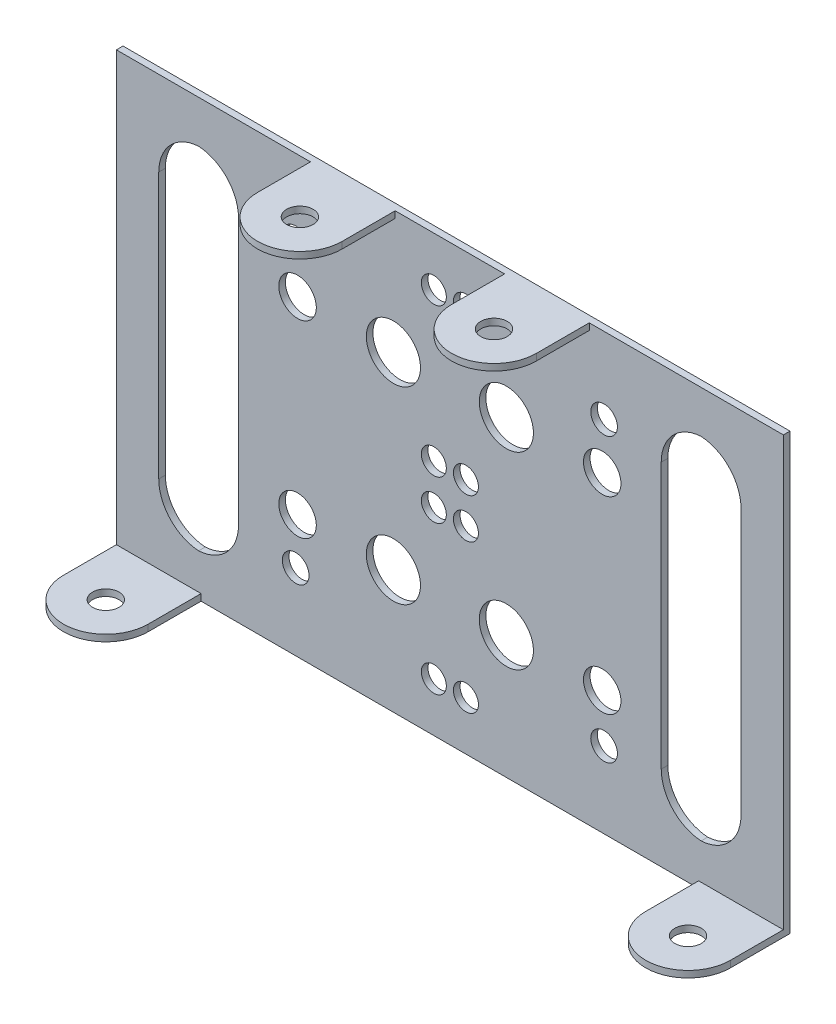
SolidWorks part; units mm, degrees
ref_plane "Front Plane" through (0, 0, 0) normal (0, 0, 1) x (1, 0, 0)
ref_plane "Top Plane" through (0, 0, 0) normal (0, 1, 0) x (1, 0, 0)
ref_plane "Right Plane" through (0, 0, 0) normal (1, 0, 0) x (0, 0, -1)
sketch "Sketch1" plane through (0, 0, 0) normal (0, 1, 0) x (1, 0, 0)
  line L0 (0, 0) -> (-69.85, 0)
  line L1 (-69.85, 0) -> (-69.85, 12.7)
  line L2 (-69.85, 12.7) -> (0, 12.7)
  line L3 (0, 12.7) -> (0, 0)
  line L4 (-69.85, 6.35) -> (-63.5, 6.35)
  line L5 (-34.925, 0) -> (-34.925, 12.7)
  line L6 (-63.5, 6.35) -> (-57.15, 6.35)
  line L7 (-57.15, 6.35) -> (-57.15, 12.7)
  line L8 (-57.15, 6.35) -> (-57.15, 0)
  line L9 (-12.7, 6.35) -> (-12.7, 0)
  line L10 (-12.7, 6.35) -> (-12.7, 12.7)
  line L11 (-6.35, 6.35) -> (-12.7, 6.35)
  circle A0 centre (-63.5, 6.35) radius 1.5875
  circle A1 centre (-6.35, 6.35) radius 1.5875
  dimension "D4" = 3.175
  dimension "D1" = 69.85
  dimension "D2" = 12.7
  dimension "D3" = 6.35
  dimension "D5" = 34.925
  dimension "D6" = 34.925
  dimension "D7" = 12.7
  dimension "D8" = 12.7
extrude "Boss-Extrude1" add sketch "Sketch1" along normal blind 1.5875 contours A0 L4 L1 L0 L8 L6 | A0 L6 L7 L2 L1 L4 | A1 L9 L0 L3 L2 L10 region at (-6.35, 0, -0.1796) region at (-63.5, 0, -3.0459) region at (-63.5, 0, -9.6541)
sketch "Sketch2" plane through (0, 0, -12.7) normal (0, 0, -1) x (-1, 0, 0)
  line L1 (0, 0) -> (69.85, 0)
  line L2 (0, 0) -> (0, 53)
  line L3 (0, 53) -> (69.85, 53)
  line L4 (69.85, 0) -> (69.85, 53)
  dimension "D1" = 69.85
  dimension "D2" = 53
extrude "Boss-Extrude2" add sketch "Sketch2" along normal blind 1.5875
sketch "Sketch3" plane through (0, 0, -14.2875) normal (0, 0, -1) x (-1, 0, 0)
  line L0 (-27.8972, 15.9448) -> (-27.8972, 27.4448)
  line L1 (-27.8972, 38.6448) -> (-27.8972, 27.4448)
  line L2 (-39.2472, 38.6448) -> (-16.5472, 38.6448)
  line L3 (-39.2472, 38.6448) -> (-39.2472, -3.3552)
  line L4 (-39.2472, -3.3552) -> (-16.5472, -3.3552)
  line L5 (-16.5472, 38.6448) -> (-16.5472, -3.3552)
  line L6 (-36.7972, 36.1448) -> (-18.9972, 36.1448)
  line L7 (-39.2472, 38.6448) -> (-36.7972, 38.6448)
  line L8 (-39.2472, 38.6448) -> (-39.2472, 36.1448)
  line L9 (-39.2472, 36.1448) -> (-36.7972, 36.1448)
  line L10 (-36.7972, 38.6448) -> (-36.7972, 36.1448)
  circle A0 centre (-27.8972, 15.9448) radius 2
  circle A1 centre (-27.8972, 27.4448) radius 3
  circle A2 centre (-36.7972, 36.1448) radius 1.25
  circle A3 centre (-18.9972, 36.1448) radius 1.25
  dimension "D1" = 4
  dimension "D5" = 6
  dimension "D7" = 11.2
  dimension "D11" = 2.5
  dimension "D13" = 2.5
  dimension "D2" = 42
  dimension "D3" = 22.7
  dimension "D4" = 11.5
  dimension "D6" = 11.2
  dimension "D8" = 11.5
  dimension "D9" = 2.5
  dimension "D10" = 2.45
  dimension "D12" = 2.45
sketch "Sketch4" plane through (0, 0, -14.2875) normal (0, 0, -1) x (-1, 0, 0)
  line L0 (0, 0) -> (69.85, 0)
  line L1 (0, 0) -> (69.85, 0) construction
  line L6 (98.3204, -4.2413) -> (56.3204, -4.2413)
  line L9 (56.3204, -26.9413) -> (56.3204, -4.2413)
  line L10 (98.3204, -26.9413) -> (56.3204, -26.9413)
  line L13 (98.3204, -26.9413) -> (98.3204, -4.2413)
  circle A4 centre (95.8204, -6.6913) radius 1.25
  circle A5 centre (95.8204, -24.4913) radius 1.25
  circle A6 centre (87.1204, -15.5913) radius 3
  circle A7 centre (75.6204, -15.5913) radius 2
  dimension "D1" = 69.85
sketch "Sketch5" plane through (0, 1.5875, 0) normal (0, 1, 0) x (1, 0, 0)
  line L0 (-6.35, 6.35) -> (-76.2, 6.35)
  line L1 (-69.85, 0) -> (-82.55, 0)
  line L2 (-69.85, 6.35) -> (-82.55, 6.35)
  line L3 (-76.2, 6.35) -> (-76.2, 12.7)
  line L4 (-69.85, 12.7) -> (-82.55, 12.7)
  line L5 (-82.55, 0) -> (-82.55, 12.7)
  line L6 (-69.85, 0) -> (-69.85, 12.7)
  circle A0 centre (-76.2, 6.35) radius 1.5875
  point P12 (-76.2, 0)
  line M3 (-69.85, 12.7) -> (-69.85, 0)
  dimension "D1" = 3.175
  dimension "D2" = 69.85
  dimension "D3" = 6.35
  dimension "D4" = 6.35
extrude "Boss-Extrude3" add sketch "Sketch5" against normal blind 1.5875 contours A0 L2 L5 L1 L0 M3 | A0 L3 L4 L5 L2 | A0 L0 L4 L3 M3 region at (-76.2, 1.5875, -3.0459) region at (-72.8959, 1.5875, -9.6541) region at (-79.5041, 1.5875, -9.6541)
sketch "Sketch6" plane through (-69.85, 0, 0) normal (-1, 0, 0) x (0, 0, 1)
  line L1 (-14.2875, 53) -> (-12.7, 53)
  line L2 (-14.2875, 53) -> (-14.2875, 0)
  line L3 (-14.2875, 0) -> (-12.7, 0)
  line L4 (-12.7, 53) -> (-12.7, 0)
extrude "Boss-Extrude4" add sketch "Sketch6" along normal blind 12.7
sketch "Sketch7" plane through (0, 1.5875, 0) normal (0, 1, 0) x (1, 0, 0)
  line L1 (-57.15, 0) -> (-69.85, 0)
  line L2 (-57.15, 0) -> (-57.15, 12.7)
  line L3 (-57.15, 12.7) -> (-69.85, 12.7)
  line L4 (-69.85, 0) -> (-69.85, 12.7)
extrude "Cut-Extrude1" cut sketch "Sketch7" against normal blind 12.7
sketch "Sketch10" plane through (0, 0, 0) normal (1, 0, 0) x (0, 0, -1)
  line L0 (0, 0) -> (0, 0.7937)
  line L1 (0, 1.5875) -> (0, 0) construction
  line L2 (0, 0.7937) -> (13.4937, 0.7938)
  line L3 (13.4937, 53) -> (13.4937, -1.4744)
  line L4 (14.2875, 53) -> (12.7, 53) construction
  line L5 (0, 0) -> (14.2875, 0)
  line L6 (14.2875, 0) -> (14.2875, 53)
  line L7 (14.2875, 53) -> (13.4937, 53)
  line M3 (0, 1.5875) -> (0, 0)
  line M4 (0, 0) -> (14.2875, 0)
  line M5 (14.2875, 0) -> (14.2875, 53)
  line M6 (14.2875, 53) -> (12.7, 53)
extrude "Cut-Extrude3" cut sketch "Sketch10" against normal through all contours L3 L2 M3 M4 | L3 M6 M4 M5 region at (0, 0.3969, -6.7469) region at (0, 26.5, -13.8906)
sketch "Sketch13" plane through (0, 0, -13.4937) normal (0, 0, -1) x (-1, 0, 0)
  line L0 (0, 0.7938) -> (23, 0.7938)
  line L1 (0, 53) -> (41.275, 53)
  line L2 (82.55, 53) -> (0, 53) construction
  line L3 (41.275, 53) -> (41.275, 0.7938)
  line L4 (41.275, 26.8969) -> (19.6299, 26.8969)
  line L5 (82.55, 0.7938) -> (0, 0.7938) construction
  line L6 (23, 0.7938) -> (23, 15.5875)
  circle A0 centre (43.2, 24.4875) radius 1.25
  circle A1 centre (43.2, 6.6875) radius 1.25
  circle A2 centre (34.5, 15.5875) radius 3
  circle A3 centre (23, 15.5875) radius 2
  circle A4 centre (39.35, 6.6875) radius 1.25
  circle A5 centre (39.35, 24.4875) radius 1.25
  circle A6 centre (48.05, 15.5875) radius 3
  circle A7 centre (59.55, 15.5875) radius 2
  circle A8 centre (59.55, 38.2063) radius 2
  circle A9 centre (48.05, 38.2063) radius 3
  circle A10 centre (39.35, 29.3063) radius 1.25
  circle A11 centre (39.35, 47.1063) radius 1.25
  circle A12 centre (23, 38.2063) radius 2
  circle A13 centre (34.5, 38.2063) radius 3
  circle A14 centre (43.2, 47.1063) radius 1.25
  circle A15 centre (43.2, 29.3063) radius 1.25
  dimension "D1" = 23
  dimension "D2" = 14.7937
extrude "Cut-Extrude4" cut sketch "Sketch13" against normal blind 12.7 contours A3 | A2 | A12 | A13 | A9 | A8 | A6 | A7 | A4 | A1 | A14 | A10 | A5 | A0 | A15 | A11 region at (-43.2, 24.4875, -13.4937) region at (-43.2, 6.6875, -13.4937) region at (-34.5, 15.5875, -13.4937) region at (-24.3742, 14.2133, -13.4937) region at (-39.35, 6.6875, -13.4937) region at (-39.35, 24.4875, -13.4937) region at (-48.05, 15.5875, -13.4937) region at (-59.55, 15.5875, -13.4937) region at (-59.55, 38.2063, -13.4937) region at (-48.05, 38.2063, -13.4937) region at (-39.35, 29.3063, -13.4937) region at (-23, 38.2063, -13.4937) region at (-34.5, 38.2063, -13.4937) region at (-43.2, 47.1063, -13.4937) region at (-43.2, 29.3063, -13.4937)
fillet "Fillet1" radius 6.35 2 edges at (-12.7, 1.1906, 0) (0, 1.1906, 0)
fillet "Fillet2" radius 6.35 2 edges at (-82.55, 1.1906, 0) (-69.85, 1.1906, 0)
sketch "Sketch14" plane through (0, 53, 0) normal (0, 1, 0) x (1, 0, 0)
  line L1 (-82.55, 12.7) -> (0, 12.7) construction
  line L2 (-34.925, 0) -> (-34.925, 12.7)
  line L3 (-47.625, 0) -> (-47.625, 12.7)
  line L4 (-47.625, 12.7) -> (-34.925, 12.7)
  line L5 (-47.625, 0) -> (-34.925, 0)
  circle A0 centre (-41.275, 6.35) radius 1.5875
  dimension "D2" = 3.175
extrude "Boss-Extrude5" add sketch "Sketch14" against normal blind 0.7937
fillet "Fillet3" radius 6.35 2 edges at (-47.625, 52.6031, 0) (-34.925, 52.6031, 0)
sketch "Sketch15" plane through (0, 0, -13.4937) normal (0, 0, -1) x (-1, 0, 0)
  line L1 (41.275, 53) -> (41.275, 0.7938)
  line L2 (82.55, 0.7938) -> (0, 0.7938) construction
  line L3 (0, 26.8969) -> (82.55, 26.8969)
  line L4 (0, 53) -> (0, 0.7938) construction
  line L5 (82.55, 53) -> (82.55, 0.7938) construction
  line L6 (41.275, 23.862) -> (41.275, 63.862)
  circle A0 centre (22.775, 43.862) radius 1.6
  circle A1 centre (59.775, 43.862) radius 1.6
  circle A2 centre (59.775, 9.9317) radius 1.6
  circle A3 centre (22.775, 9.9317) radius 1.6
  point P18 (41.275, 43.862)
  dimension "D1" = 3.2
  dimension "D3" = 3.2
  dimension "D2" = 37
extrude "Cut-Extrude7" cut sketch "Sketch15" against normal blind 0.7937 contours A0 | A3 | A2 | A1 region at (-22.775, 43.862, -13.4937) region at (-59.775, 43.862, -13.4937) region at (-59.775, 9.9317, -13.4937) region at (-22.775, 9.9317, -13.4937)
sketch "Sketch16" plane through (0, 53, 0) normal (0, 1, 0) x (1, 0, 0)
  line L0 (-41.275, 6.35) -> (-41.275, 13.4937)
  line L3 (-82.55, 13.4937) -> (0, 13.4937) construction
  line L5 (-57.9967, 6.35) -> (-57.9967, 12.7)
  line L6 (-82.55, 12.7) -> (-47.625, 12.7) construction
  line L7 (-57.9967, 12.7) -> (-47.8367, 12.7)
  line L8 (-47.8367, 12.7) -> (-47.8367, 6.35)
  line L9 (-34.7133, 12.7) -> (-34.7133, 6.35)
  line L10 (-24.5533, 6.35) -> (-24.5533, 12.7)
  line L11 (-34.7133, 12.7) -> (-24.5533, 12.7)
  circle A0 centre (-52.9167, 6.35) radius 1.5875
  circle A1 centre (-29.6333, 6.35) radius 1.5875
  arc A2 (-57.9967, 6.35) -> (-47.8367, 6.35) centre (-52.9167, 6.35) ccw
  arc A3 (-24.5533, 6.35) -> (-34.7133, 6.35) centre (-29.6333, 6.35) cw
  line M5 (-34.925, 12.7) -> (0, 12.7)
  line M9 (-82.55, 12.7) -> (-47.625, 12.7)
  dimension "D1" = 23.2833
  dimension "D4" = 3.175
  dimension "D2" = 11.6417
  dimension "D3" = 5.08
extrude "Boss-Extrude6" add sketch "Sketch16" against normal blind 0.7937 contours L5 A2 L8 A0 M9 | A3 L10 L9 A1 M5 region at (-57.8437, 53, -9.525) region at (-29.6333, 53, -12.5471)
sketch "Sketch17" plane through (0, 53, 0) normal (0, 1, 0) x (1, 0, 0)
  line L1 (-47.625, 12.7) -> (-34.925, 12.7)
  line L2 (-47.625, 12.7) -> (-47.625, -2.2335)
  line L3 (-47.625, -2.2335) -> (-34.925, -2.2335)
  line L4 (-34.925, 12.7) -> (-34.925, -2.2335)
  dimension "D1" = 12.7
extrude "Cut-Extrude8" cut sketch "Sketch17" against normal blind 0.7937
sketch "Sketch18" plane through (0, 1.5875, 0) normal (0, 1, 0) x (1, 0, 0)
  line L0 (-76.2, 6.35) -> (-76.2, 7.9375)
  line L1 (-81.28, 6.35) -> (-81.28, 12.7)
  line L2 (-82.55, 12.7) -> (-57.9967, 12.7) construction
  line L3 (-81.28, 12.7) -> (-82.55, 12.7)
  line L4 (-82.55, 13.4937) -> (0, 13.4937)
  line L5 (-41.275, 13.4937) -> (-41.275, 0)
  line L6 (-82.55, 6.35) -> (-82.55, 12.7)
  line L7 (-71.12, 6.35) -> (-71.12, 12.7)
  line L8 (-69.85, 6.35) -> (-69.85, 12.7)
  line L9 (-71.12, 12.7) -> (-69.85, 12.7)
  line L10 (-11.43, 12.7) -> (-12.7, 12.7)
  line L11 (-12.7, 6.35) -> (-12.7, 12.7)
  line L12 (-11.43, 6.35) -> (-11.43, 12.7)
  line L13 (0, 6.35) -> (0, 12.7)
  line L14 (-1.27, 12.7) -> (0, 12.7)
  line L15 (-1.27, 6.35) -> (-1.27, 12.7)
  line L16 (-6.35, 6.35) -> (-6.35, 7.9375)
  arc A0 (-81.28, 6.35) -> (-71.12, 6.35) centre (-76.2, 6.35) ccw
  circle A1 centre (-76.2, 6.35) radius 1.5875 construction
  arc A2 (-82.55, 6.35) -> (-69.85, 6.35) centre (-76.2, 6.35) ccw
  arc A3 (0, 6.35) -> (-12.7, 6.35) centre (-6.35, 6.35) cw
  arc A4 (-1.27, 6.35) -> (-11.43, 6.35) centre (-6.35, 6.35) cw
  line M1 (-82.55, 12.7) -> (-82.55, 6.35)
  arc M2 (-82.55, 6.35) -> (-76.2, 0) centre (-76.2, 6.35) ccw
  arc M3 (-76.2, 0) -> (-69.85, 6.35) centre (-76.2, 6.35) ccw
  line M4 (-69.85, 6.35) -> (-69.85, 12.7)
  line M5 (-69.85, 12.7) -> (-82.55, 12.7)
extrude "Cut-Extrude9" cut sketch "Sketch18" against normal blind 0.7937 contours A0 L1 L7 M5 M1 M2 M3 M4 | L15 A4 L12 L10 L11 A3 L13 L14 region at (-76.2, 1.5875, -1.0904) region at (-11.6096, 1.5875, -9.525) body kept at (-34.7133, 53, -12.7)
sketch "Sketch19" plane through (0, 0, -12.7) normal (0, 0, 1) x (1, 0, 0)
  line L0 (-82.55, 0.7937) -> (-41.275, 0.7937)
  line L1 (-81.28, 0.7937) -> (-82.55, 0.7937)
  line L2 (-81.28, 0.7937) -> (-81.28, 53)
  line L3 (-81.28, 53) -> (-82.55, 53)
  line L4 (-82.55, 0.7937) -> (-82.55, 53)
  line L5 (-71.12, 0.7937) -> (-11.43, 0.7937) construction
  line L6 (-41.275, 0.7937) -> (-41.275, -14.5585)
  line L7 (0, 0.7937) -> (0, 53)
  line L8 (-1.27, 53) -> (0, 53)
  line L9 (-1.27, 0.7937) -> (-1.27, 53)
  line L10 (-1.27, 0.7937) -> (0, 0.7937)
  line M15 (-57.9967, 53) -> (-82.55, 53)
  line M16 (-82.55, 53) -> (-82.55, 0.7937)
  line M17 (-82.55, 0.7937) -> (-81.28, 0.7938)
  line M18 (-81.28, 0.7938) -> (-81.28, 1.5875)
extrude "Cut-Extrude11" cut sketch "Sketch19" against normal blind 0.7937 contours L2 M18 M15 M16 M17 | L7 L8 L9 L10 region at (-81.915, 26.8969, -12.7)
sketch "Sketch21" plane through (0, 0, -12.7) normal (0, 0, 1) x (1, 0, 0)
  line L0 (-41.275, 53) -> (-41.275, 0.7937)
  line L1 (-47.8367, 53) -> (-34.7133, 53) construction
  line L2 (-71.12, 0.7937) -> (-11.43, 0.7937) construction
  line L3 (-81.28, 1.5875) -> (-81.28, 53) construction
  line L4 (-66.63, 47.92) -> (-76.2, 47.92)
  line L5 (-76.2, 47.92) -> (-76.2, 26.9375)
  line L6 (-15.92, 5.8738) -> (-15.92, 47.92)
  line L7 (-76.2, 26.9375) -> (-76.2, 5.8738)
  line L8 (-6.35, 5.8737) -> (-15.92, 5.8738)
  line L9 (-76.2, 5.8738) -> (-66.63, 5.8738)
  line L10 (-66.63, 5.8738) -> (-66.63, 47.92)
  line L11 (-81.28, 53) -> (-57.9967, 53) construction
  line L12 (-6.35, 26.9375) -> (-6.35, 5.8737)
  line L13 (-6.35, 47.92) -> (-6.35, 26.9375)
  line L14 (-15.92, 47.92) -> (-6.35, 47.92)
  dimension "D2" = 5.08
  dimension "D5" = 5.08
  dimension "D7" = 5.08
extrude "Cut-Extrude12" cut sketch "Sketch21" against normal blind 0.7937 contours L9 L10 L4 L5 L7 | L14 L6 L8 L12 L13 region at (-71.415, 26.8969, -12.7) region at (-11.135, 26.8969, -12.7)
fillet "Fillet4" radius 5.08 2 edges at (-76.2, 47.92, -13.0969) (-66.63, 47.92, -13.0969)
fillet "Fillet5" radius 5.08 6 edges at (-6.35, 47.92, -13.0969) (-15.92, 47.92, -13.0969) (-15.92, 5.8738, -13.0969) (-6.35, 5.8737, -13.0969) (-66.63, 5.8738, -13.0969) (-76.2, 5.8738, -13.0969)
sketch "Sketch22" plane through (0, 0, -13.4937) normal (0, 0, -1) x (-1, 0, 0)
  line L0 (41.275, 0.7938) -> (41.275, 32.031)
  line L1 (81.28, 0.7938) -> (1.27, 0.7937) construction
  line L2 (1.27, 26.8969) -> (41.275, 26.8969)
  line L3 (1.27, 0.7937) -> (1.27, 53) construction
  circle A0 centre (39.35, 6.6875) radius 1.5
  circle A1 centre (39.35, 24.4875) radius 1.5
  circle A2 centre (34.5, 15.5875) radius 3.25
  circle A3 centre (23, 15.5875) radius 2.25
  circle A5 centre (39.35, 47.1063) radius 1.5
  circle A6 centre (39.35, 29.3063) radius 1.5
  circle A7 centre (34.5, 38.2063) radius 3.25
  circle A8 centre (23, 38.2063) radius 2.25
  circle A9 centre (59.55, 38.2063) radius 2.25
  circle A10 centre (48.05, 38.2063) radius 3.25
  circle A11 centre (43.2, 29.3063) radius 1.5
  circle A12 centre (43.2, 47.1063) radius 1.5
  circle A13 centre (59.55, 15.5875) radius 2.25
  circle A14 centre (48.05, 15.5875) radius 3.25
  circle A15 centre (43.2, 24.4875) radius 1.5
  circle A16 centre (43.2, 6.6875) radius 1.5
  circle M8 centre (43.2, 24.4875) radius 1.25
  circle M9 centre (39.35, 24.4875) radius 1.25
  circle M10 centre (43.2, 6.6875) radius 1.25
  circle M11 centre (39.35, 6.6875) radius 1.25
  circle M12 centre (59.55, 15.5875) radius 2
  circle M13 centre (48.05, 15.5875) radius 3
  circle M14 centre (48.05, 38.2063) radius 3
  circle M15 centre (34.5, 38.2063) radius 3
  circle M16 centre (23, 38.2063) radius 2
  circle M17 centre (23, 15.5875) radius 2
  circle M18 centre (34.5, 15.5875) radius 3
  circle M19 centre (59.55, 38.2063) radius 2
  circle M20 centre (43.2, 47.1063) radius 1.25
  circle M21 centre (39.35, 29.3063) radius 1.25
  circle M22 centre (43.2, 29.3063) radius 1.25
  circle M23 centre (39.35, 47.1063) radius 1.25
  dimension "D1" = 3
  dimension "D2" = 3
  dimension "D3" = 4.5
  dimension "D4" = 6.5
extrude "Cut-Extrude13" cut sketch "Sketch22" against normal blind 0.7937 contours A8 M16 | A7 M15 | A5 M23 | A12 M20 | A10 M14 | A9 M19 | A13 M12 | A0 M11 | A16 M10 | A2 M18 | A14 M13 | A1 M9 | A15 M8 | A11 M22 | A6 M21 | A3 M17 region at (-37.8924, 6.6875, -13.4937) region at (-37.8924, 24.4875, -13.4937) region at (-31.3419, 15.5875, -13.4937) region at (-20.8136, 15.5875, -13.4937) region at (-37.8924, 47.1063, -13.4937) region at (-37.8924, 29.3063, -13.4937) region at (-31.3419, 38.2063, -13.4937) region at (-20.8136, 38.2063, -13.4937) region at (-57.3636, 38.2063, -13.4937) region at (-44.8919, 38.2063, -13.4937) region at (-41.7424, 29.3063, -13.4937) region at (-41.7424, 47.1063, -13.4937) region at (-57.3636, 15.5875, -13.4937) region at (-44.8919, 15.5875, -13.4937) region at (-41.7424, 24.4875, -13.4937) region at (-41.7424, 6.6875, -13.4937)
